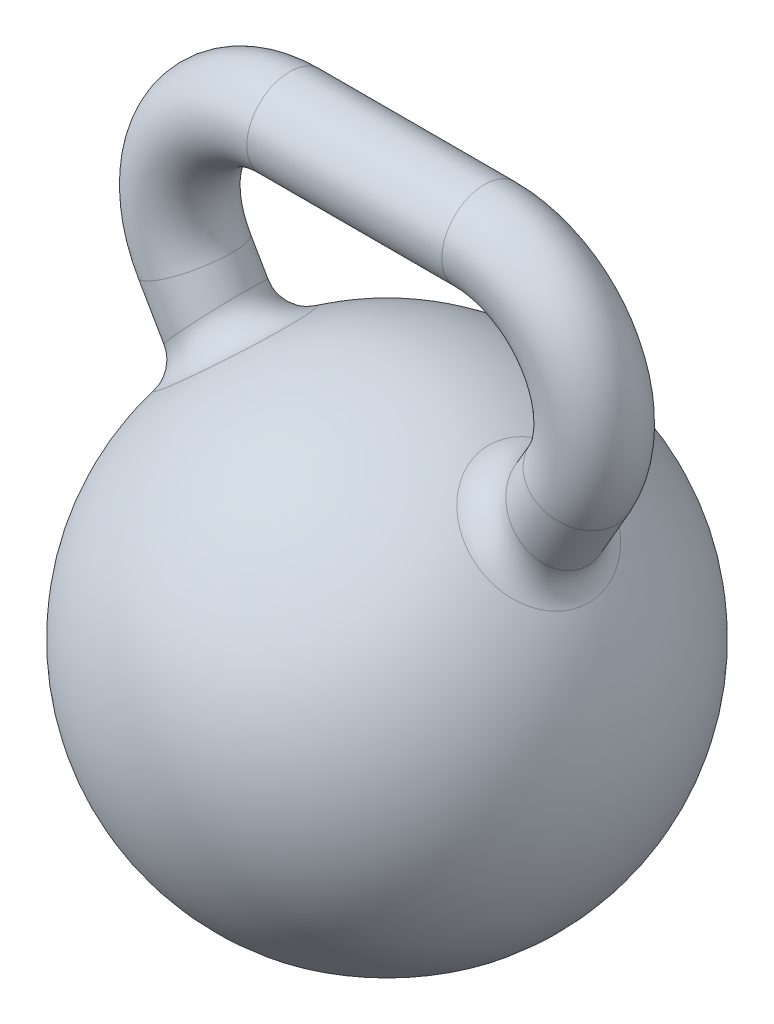
SolidWorks part; units mm, degrees
ref_plane "Front Plane" through (0, 0, 0) normal (0, 0, 1) x (1, 0, 0)
ref_plane "Top Plane" through (0, 0, 0) normal (0, 1, 0) x (1, 0, 0)
ref_plane "Right Plane" through (0, 0, 0) normal (1, 0, 0) x (0, 0, -1)
sketch "Sketch1" plane through (0, 0, 0) normal (0, 0, 1) x (1, 0, 0)
  line L0 (0, 0) -> (63.7535, 0)
  line L1 (0, 147.5493) -> (0, 109.4258) construction
  line L2 (0, 0) -> (0, 177.8)
  arc A0 (63.7535, 0) -> (0, 177.8) centre (0, 77.47) ccw
  point P8 (0, 0)
  dimension "D1" = 100.33
  dimension "D2" = 77.47
revolve "Revolve3" add sketch "Sketch1" angle 360 about L1
sketch "Sketch2" plane through (0, 0, 0) normal (0, 0, 1) x (1, 0, 0)
  line L0 (-79.5811, 138.5679) -> (-95.6326, 166.37)
  line L1 (0, 0) -> (0, 223.1967) construction
  line L2 (-40.64, 261.62) -> (40.64, 261.62)
  line L3 (79.5811, 138.5679) -> (95.6326, 166.37)
  arc A0 (63.7535, 0) -> (-63.7535, 0) centre (0, 77.47) ccw construction
  arc A1 (-95.6326, 166.37) -> (-40.64, 261.62) centre (-40.64, 198.12) cw
  arc A2 (95.6326, 166.37) -> (40.64, 261.62) centre (40.64, 198.12) ccw
  point P15 (0, 261.62)
  dimension "D3" = 63.5
  dimension "D1" = 30
  dimension "D2" = 40.64
  dimension "D4" = 261.62
sketch "Sketch3" plane through (0, 0, 0) normal (1, 0, 0) x (0, 0, -1)
  circle A0 centre (0, 243.84) radius 17.78
  point P2 (0, 261.62)
  point P3 (0, 0)
  dimension "D1" = 35.56
sweep "Sweep1" add profiles "Sketch3" path "Sketch2"
sweep "Sweep2" add profiles "Sketch3<2>" path "Sketch2<2>"
sketch "Sketch3<2>" plane through (0, 0, 0) normal (1, 0, 0) x (0, 0, -1) same geometry as "Sketch3"
sketch "Sketch2<2>" plane through (0, 0, 0) normal (0, 0, 1) x (1, 0, 0) same geometry as "Sketch2"
fillet "Fillet1" radius 12.7 2 edges at (-56.9204, 159.0554, 13.0383) (77.9604, 140.0526, 8.4678)
